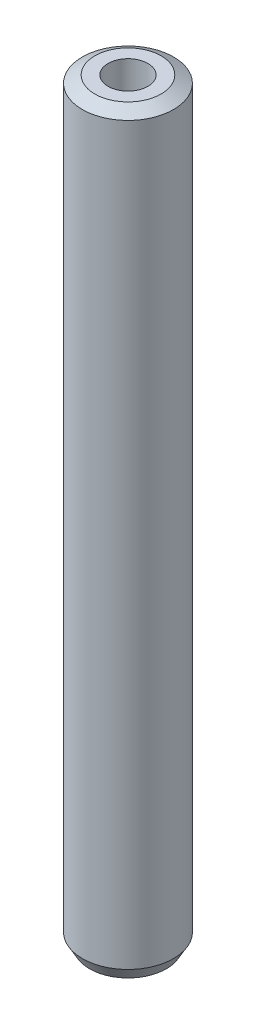
SolidWorks part; units mm, degrees
ref_plane "Front Plane" through (0, 0, 0) normal (0, 0, 1) x (1, 0, 0)
ref_plane "Top Plane" through (0, 0, 0) normal (0, 1, 0) x (1, 0, 0)
ref_plane "Right Plane" through (0, 0, 0) normal (1, 0, 0) x (0, 0, -1)
sketch "Sketch1" plane through (0, 0, 0) normal (0, 1, 0) x (1, 0, 0)
  circle A0 centre (0, 0) radius 27.5
  dimension "SHAFT_OD" = 55
extrude "Boss-Extrude1" add sketch "Sketch1" along normal blind 455.3073
sketch "Sketch2" plane through (0, 0, 0) normal (0, 1, 0) x (1, 0, 0)
  circle A0 centre (0, 0) radius 12.0034
  dimension "BORE_D" = 24.0068
extrude "Cut-Extrude1" cut sketch "Sketch2" along normal through all
chamfer "Chamfer1" distance 4.3462 angle 60 2 edges at (0, 455.3073, 27.5) (0, 0, 27.5) first distance on face at (0, 455.3073, 27.5) first distance on face at (0, 0, 12.0034)
